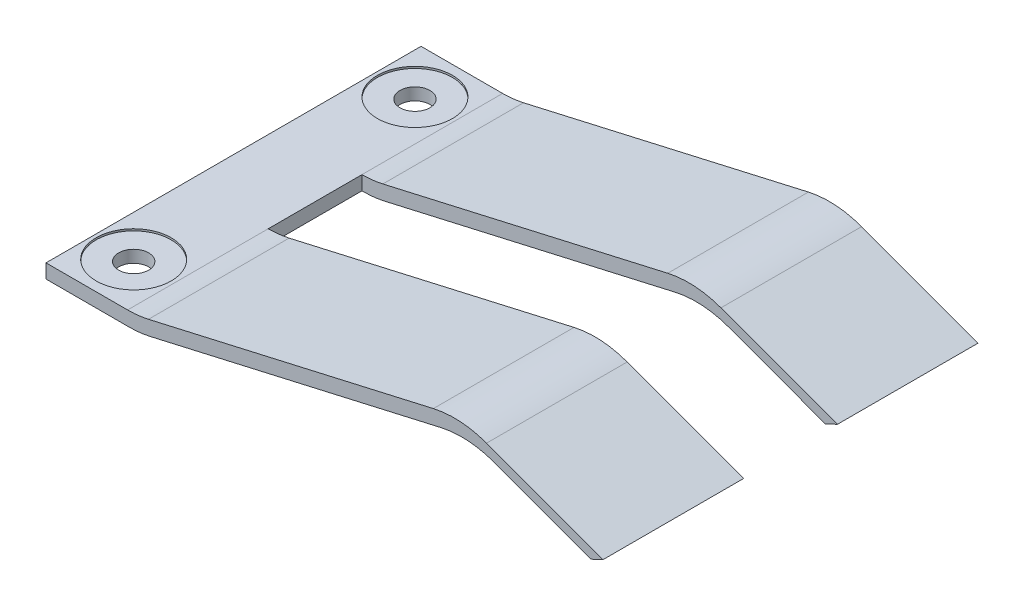
SolidWorks part; units mm, degrees
ref_plane "前视基准面" through (0, 0, 0) normal (0, 0, 1) x (1, 0, 0)
ref_plane "上视基准面" through (0, 0, 0) normal (0, 1, 0) x (1, 0, 0)
ref_plane "右视基准面" through (0, 0, 0) normal (1, 0, 0) x (0, 0, -1)
other "Configuration Table"
sketch "草图1" plane through (0, 0, 0) normal (0, 0, 1) x (1, 0, 0)
  line L0 (0, 0) -> (10, 0)
  line L1 (10, 0) -> (45, 8)
  line L2 (45, 8) -> (60, 2.5)
  line L3 (0, 0) -> (0, 1.5)
  line L4 (0, 1.5) -> (9.8308, 1.5)
  line L5 (9.8308, 1.5) -> (44.2044, 9.3568)
  line L6 (44.2044, 9.3568) -> (60, 3.5651)
  line L7 (60, 3.5651) -> (60, 2.5)
  dimension "D1" = 10
  dimension "D2" = 35
  dimension "D3" = 2.5
  dimension "D4" = 8
  dimension "D5" = 15
  dimension "D6" = 1.5
  dimension "D7" = 1.5
  dimension "D8" = 1
extrude "凸台-拉伸1" add sketch "草图1" along normal blind 40
fillet "圆角1" radius 10 4 edges at (44.2044, 9.3568, 20) (45, 8, 20) (10, 0, 20) (9.8308, 1.5, 20)
chamfer "倒角1" distance 2 angle 45 1 edges at (60, 2.5, 20) first distance on face at (53.891, 4.74, 20)
sketch "草图2" plane through (0, 1.5, 0) normal (0, 1, 0) x (1, 0, 0)
  line L0 (4.3512, 0) -> (4.3512, -40) construction
  line L1 (8.7024, 0) -> (0, 0) construction
  line L2 (8.7024, -40) -> (0, -40) construction
  line L3 (4.3512, -20) -> (0, -20) construction
  line L4 (0, -40) -> (0, 0) construction
  circle A0 centre (4.3512, -5) radius 1.6
  circle A1 centre (4.3512, -35) radius 1.6
  dimension "D1" = 30
  dimension "D2" = 3.2
extrude "切除-拉伸1" cut sketch "草图2" against normal up to next
sketch "草图3" plane through (0, 1.5, 0) normal (0, 1, 0) x (1, 0, 0)
  circle A0 centre (4.3512, -5) radius 4
  circle A1 centre (4.3512, -35) radius 4
  dimension "D1" = 8
extrude "切除-拉伸2" cut sketch "草图3" against normal blind 0.2
sketch "草图4" plane through (0, 1.5, 0) normal (0, 1, 0) x (1, 0, 0)
  line L0 (59.4054, -40) -> (59.4054, 0) construction
  line L1 (59.4054, -15) -> (8.7024, -15)
  line L2 (59.4054, -15) -> (59.4054, -25)
  line L3 (59.4054, -25) -> (8.7024, -25)
  line L4 (8.7024, -15) -> (8.7024, -25)
  line L5 (8.7024, -40) -> (8.7024, 0) construction
  line L6 (0, -20) -> (59.4054, -20) construction
  line L7 (0, -40) -> (0, 0) construction
  dimension "D1" = 10
extrude "切除-拉伸3" cut sketch "草图4" against normal up to next and the other way up to next
